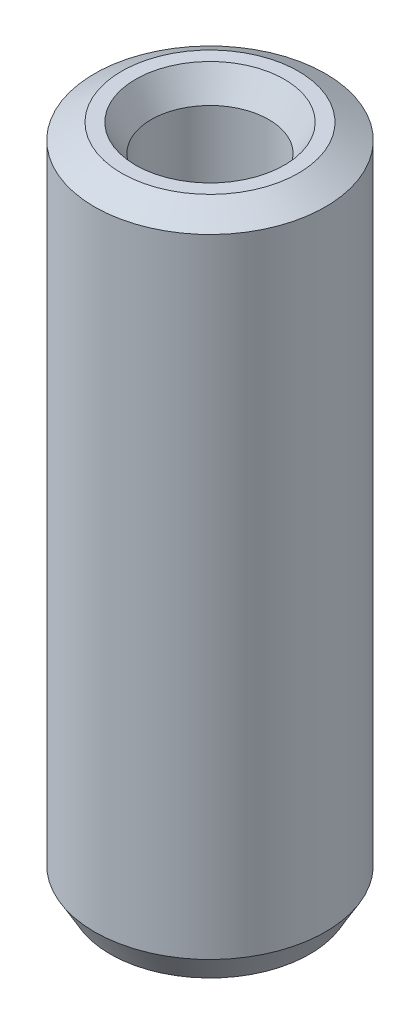
SolidWorks part; units mm, degrees
ref_plane "Front Plane" through (0, 0, 0) normal (0, 0, 1) x (1, 0, 0)
ref_plane "Top Plane" through (0, 0, 0) normal (0, 1, 0) x (1, 0, 0)
ref_plane "Right Plane" through (0, 0, 0) normal (1, 0, 0) x (0, 0, -1)
sketch "Sketch1" plane through (0, 0, 0) normal (0, 1, 0) x (1, 0, 0)
  circle A0 centre (0, 0) radius 17.5
  dimension "SLEEVE_OD" = 35
extrude "Boss-Extrude1" add sketch "Sketch1" along normal blind 101.6325
sketch "Sketch2" plane through (0, 0, 0) normal (0, 1, 0) x (1, 0, 0)
  circle A0 centre (0, 0) radius 8.9108
  dimension "BORE_D" = 17.8217
extrude "Cut-Extrude1" cut sketch "Sketch2" along normal through all
chamfer "Chamfer1" distance 2.3669 angle 60 4 edges at (0, 101.6325, 8.9108) (0, 0, 8.9108) (0, 0, 17.5) (0, 101.6325, 17.5) first distance on face at (0, 101.6325, 8.9108) first distance on face at (0, 0, 8.9108) first distance on face at (0, 101.6325, 17.5)
